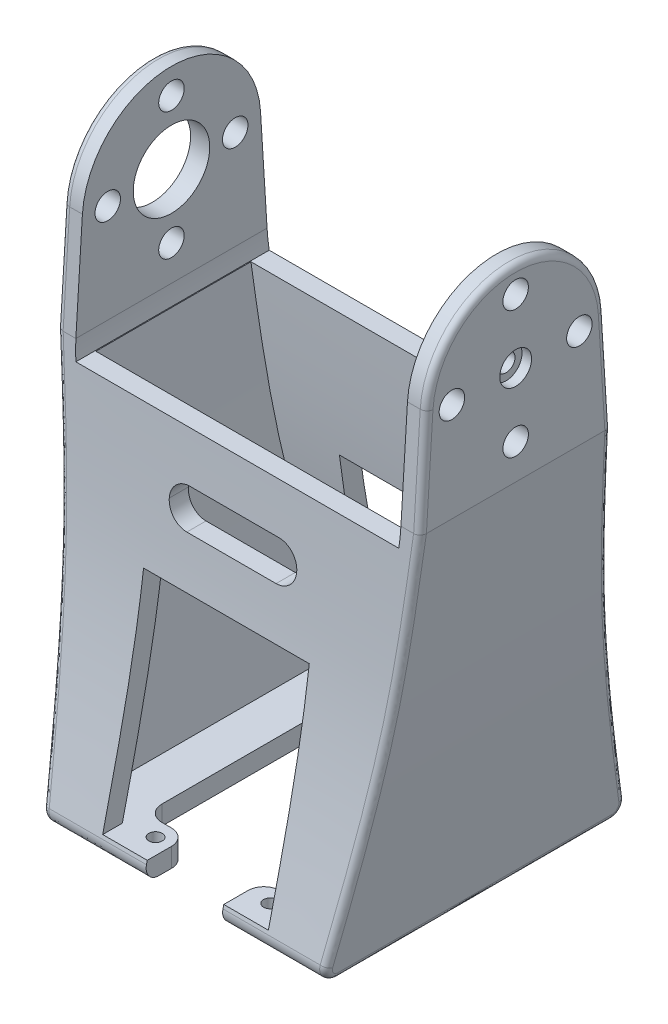
SolidWorks part; units mm, degrees
material "Esun Hard Tough Resin"
ref_plane "Front Plane" through (0, 0, 0) normal (0, 0, 1) x (1, 0, 0)
ref_plane "Top Plane" through (0, 0, 0) normal (0, 1, 0) x (1, 0, 0)
ref_plane "Right Plane" through (0, 0, 0) normal (1, 0, 0) x (0, 0, -1)
sketch "Sketch2" plane through (0, 0, 0) normal (0, 1, 0) x (1, 0, 0)
  line L1 (22, -24) -> (-22, -24)
  line L2 (22, -24) -> (22, 24)
  line L3 (22, 24) -> (-22, 24)
  line L4 (-22, -24) -> (-22, 24)
  line L5 (22, -24) -> (-22, 24) construction
  line L6 (22, 24) -> (-22, -24) construction
  point P0 (0, 0)
  dimension "D1" = 48
  dimension "D2" = 44
ref_plane "Plane1" through (0, 60, 0) normal (0, 1, 0) x (1, 0, 0)
ref_plane "Plane6" through (0, 35, 0) normal (0, 1, 0) x (1, 0, 0)
sketch "Sketch29" plane through (0, 35, 0) normal (0, 1, 0) x (1, 0, 0)
  line L1 (-26, -17) -> (26, -17)
  line L2 (-26, -17) -> (-26, 17)
  line L3 (-26, 17) -> (26, 17)
  line L4 (26, -17) -> (26, 17)
  line L5 (-26, -17) -> (26, 17) construction
  line L6 (-26, 17) -> (26, -17) construction
  point P0 (0, 0)
  dimension "D1" = 52
  dimension "D2" = 34
sketch "Sketch3" plane through (0, 60, 0) normal (0, 1, 0) x (1, 0, 0)
  line L1 (28.5, -15) -> (-28.5, -15)
  line L2 (28.5, -15) -> (28.5, 15)
  line L3 (28.5, 15) -> (-28.5, 15)
  line L4 (-28.5, -15) -> (-28.5, 15)
  line L5 (28.5, -15) -> (-28.5, 15) construction
  line L6 (28.5, 15) -> (-28.5, -15) construction
  point P0 (0, 0)
  dimension "D1" = 57
  dimension "D2" = 30
loft "Loft1" add profiles "Sketch2", "Sketch29", "Sketch3" connector at (-22, 0, 24) connector at (-26, 35, 17) connector at (-28.5, 60, 15)
shell "Shell1" thickness 3
ref_plane "Plane2" through (0, 0, 25.5) normal (0, 0, 1) x (1, 0, 0)
ref_plane "Plane3" through (0, 0, 24) normal (0, 0, 1) x (1, 0, 0)
sketch "Sketch19" plane through (0, 60, 0) normal (0, 1, 0) x (1, 0, 0)
  line L0 (28.5, -15) -> (-28.5, -15) construction
  line L1 (28.5, -15) -> (28.5, 15) construction
  line L2 (28.5, 15) -> (-28.5, 15) construction
  line L3 (-28.5, -15) -> (-28.5, 15) construction
  line L4 (28.5, -15) -> (-28.5, -15)
  line L5 (28.5, -15) -> (28.5, 15)
  line L6 (28.5, 15) -> (-28.5, 15)
  line L7 (-28.5, -15) -> (-28.5, 15)
extrude "Boss-Extrude4" add sketch "Sketch19" along normal blind 30 separate body
sketch "Sketch21" plane through (0, 90, 0) normal (0, 1, 0) x (1, 0, 0)
  line L0 (28.5, 15) -> (-28.5, 15) construction
  line L1 (25.5, -15) -> (-25.5, -15)
  line L2 (25.5, -15) -> (25.5, 15)
  line L3 (25.5, 15) -> (-25.5, 15)
  line L4 (-25.5, -15) -> (-25.5, 15)
  line L5 (25.5, -15) -> (-25.5, 15) construction
  line L6 (25.5, 15) -> (-25.5, -15) construction
  point P0 (0, 0)
  dimension "D1" = 51
extrude "Cut-Extrude15" cut sketch "Sketch21" against normal blind 30
sketch "Sketch22" plane through (0, 0, 0) normal (1, 0, 0) x (0, 0, -1)
  line L0 (15, 90) -> (-15, 90) construction
  line L1 (15, 90) -> (-15, 90)
  line L2 (13.9725, 76.3766) -> (15, 60)
  line L3 (15, 60) -> (15, 90)
  line L4 (-15, 90) -> (-15, 60)
  line L5 (-15, 60) -> (-13.9725, 76.3766)
  circle A0 centre (0, 75.5) radius 6
  circle A1 centre (0, 75.5) radius 10 construction
  circle A2 centre (0, 75.5) radius 14
  circle A3 centre (0, 85.5) radius 2
  circle A4 centre (-10, 75.5) radius 2
  circle A5 centre (0, 65.5) radius 2
  circle A6 centre (10, 75.5) radius 2
  point P6 (0, 90)
  dimension "D1" = 28
  dimension "D2" = 20
  dimension "D3" = 12
  dimension "D4" = 4
  dimension "D5" = 14.5
extrude "Cut-Extrude17" cut sketch "Sketch22" against normal through all contours A2 L2 L3 L1 L4 L5 | A6 | A5 | A4 | A0 | A3 region at (0, 75, -14.5757) region at (0, 75.5, 0) region at (0, 85.5, 0) region at (0, 75.5, 10) region at (0, 65.5, 0) region at (0, 75.5, -10)
sketch "Sketch23" plane through (0, 0, 24) normal (0, 0, 1) x (1, 0, 0)
  line L2 (25.3312, 57) -> (-25.3312, 57)
  line L12 (0, 0) -> (0, 60) construction
  line L17 (-25.5, 76.3766) -> (-25.5, 60) construction
  line L19 (-25.5, 60) -> (25.5, 60)
  line L22 (-25.5, 76.3766) -> (-25.5, 60) construction
  arc A0 (-25.5, 60) -> (-25.3312, 57) centre (1.2382, 60) ccw
  arc A1 (25.5, 60) -> (25.3312, 57) centre (-1.2382, 60) cw
  dimension "D1" = 3
extrude "Cut-Extrude26" cut sketch "Sketch23" against normal through all contours L2 L12 | L12 L2 | L2 A0 L19 A1 region at (0, 58.5017, 24)
sketch "Sketch24" plane through (-28.5, 0, 0) normal (-1, 0, 0) x (0, 0, 1)
  circle A0 centre (0, 85.5) radius 2
  circle A1 centre (10, 75.5) radius 2
  circle A2 centre (0, 65.5) radius 2
  circle A3 centre (-10, 75.5) radius 2
  dimension "D1" = 4
extrude "Cut-Extrude19" cut sketch "Sketch24" against normal through all
fillet "Fillet8" radius 2 2 edges
fillet "Fillet9" radius 1 10 edges at (22.1102, 0.9293, -23.1632) (-22.069, 0.5817, -22.884) (22.069, 0.5817, 22.884) (-22.1102, 0.9293, 23.1632)
sketch "Sketch25" plane through (28.5, 0, 0) normal (1, 0, 0) x (0, 0, -1)
  line L5 (-15, 90) -> (15, 90)
  line L7 (-13.9725, 76.3766) -> (-15, 60)
  line L8 (13.9725, 76.3766) -> (15, 60)
  line L9 (15, 60) -> (15, 90)
  line L10 (-15, 90) -> (-15, 60)
  arc A0 (13.9725, 76.3766) -> (-13.9725, 76.3766) centre (0, 75.5) ccw construction
  arc A1 (13.9725, 76.3766) -> (-13.9725, 76.3766) centre (0, 75.5) ccw
  circle A2 centre (0, 75.5) radius 6 construction
  circle A3 centre (0, 75.5) radius 6 construction
  circle A4 centre (0, 75.5) radius 1.4
  dimension "D1" = 2.8
extrude "Cut-Extrude20" cut sketch "Sketch25" against normal up to next (3 mm away)
sketch "Sketch26" plane through (28.5, 0, 0) normal (1, 0, 0) x (0, 0, -1)
  circle A0 centre (0, 75.5) radius 2.5
  dimension "D1" = 5
extrude "Cut-Extrude21" cut sketch "Sketch26" against normal blind 1.5
ref_plane "Plane4" through (0, 0, 23.4208) normal (0, 0, 1) x (1, 0, 0)
sketch "Sketch28" plane through (0, 0, 23.4208) normal (0, 0, 1) x (1, 0, 0)
  line L0 (0, 0) -> (0, 57) construction
  line L1 (-13, 3) -> (13, 3)
  line L2 (-13, 3) -> (-13, 36)
  line L3 (-13, 36) -> (13, 36)
  line L4 (13, 3) -> (13, 36)
  line L5 (-13, 3) -> (13, 36) construction
  line L6 (-13, 36) -> (13, 3) construction
  line L7 (-19.3346, 3) -> (19.3346, 3) construction
  line L8 (25.3312, 57) -> (-25.3312, 57) construction
  point P0 (0, 19.5)
  point P9 (0, 0)
  dimension "D1" = 33
  dimension "D2" = 26
extrude "Cut-Extrude23" cut sketch "Sketch28" against normal through all and the other way blind 10
sketch "Sketch30" plane through (0, 0, 24) normal (0, 0, 1) x (1, 0, 0)
  line L1 (-10, 43.5) -> (10, 43.5)
  line L2 (-10, 43.5) -> (-10, 49.5)
  line L3 (-10, 49.5) -> (10, 49.5)
  line L4 (10, 43.5) -> (10, 49.5)
  line L5 (-10, 43.5) -> (10, 49.5) construction
  line L6 (-10, 49.5) -> (10, 43.5) construction
  line L7 (0, 36) -> (0, 57) construction
  line L8 (-13, 36) -> (13, 36) construction
  line L9 (25.3312, 57) -> (-25.3312, 57) construction
  point P0 (0, 46.5)
  point P5 (0, 42.604)
  point P13 (0, 46.5)
  dimension "D1" = 6
  dimension "D2" = 20
extrude "Cut-Extrude27" cut sketch "Sketch30" against normal up to surface (10.9194 mm away) contours L3 L4 L1 L2 up to face at (-3.8528, 24.6718, 16.1355)
fillet "Fillet12" radius 3 4 edges at (10, 43.5, 14.5862) (10, 49.5, 14.1251) (-10, 49.5, 14.1251) (-10, 43.5, 14.5862)
sketch "Sketch13" plane through (0, 0, 0) normal (0, 1, 0) x (1, 0, 0)
  line L4 (-8.5007, 19.5) -> (-6.0007, 19.5) construction
  line L5 (-6.0007, 23.474) -> (-6.0007, 19.7118)
  line L32 (0, -23.4208) -> (0, 23.474) construction
  line L33 (-32.8899, -23.4208) -> (32.8899, -23.4208) construction
  line L36 (-6.0007, 23.474) -> (6.0007, 23.474)
  line L37 (-8.5007, 17.2118) -> (-10.0007, 17.2118)
  line L38 (-12.5007, 14.7118) -> (-12.5007, -14.5)
  line L41 (21.1115, 21.474) -> (21.1115, -21.474) construction
  line L45 (12.5007, 14.7118) -> (12.5007, -14.5)
  line L46 (8.5007, 17.2118) -> (10.0007, 17.2118)
  line L47 (6.0007, 23.474) -> (6.0007, 19.7118)
  line L48 (-6.0007, -23.474) -> (-6.0007, -19.5)
  line L49 (-8.5007, -17) -> (-10.0007, -17)
  line L50 (8.5007, -17) -> (10.0007, -17)
  line L51 (6.0007, -23.474) -> (6.0007, -19.5)
  line L52 (-6.0007, -23.474) -> (6.0007, -23.474)
  line L53 (21.2301, 23.474) -> (-21.2301, 23.474) construction
  line L60 (-21.2301, -23.474) -> (21.2301, -23.474) construction
  circle A0 centre (-8.5007, -8.8) radius 1.05
  circle A1 centre (-8.5007, -19.5) radius 1.05
  circle A2 centre (9.4993, -19.4996) radius 1.05
  circle A3 centre (9.4993, -8.8) radius 1.05
  circle A4 centre (-8.5007, 19.5) radius 1.05
  circle A5 centre (9.4993, 19.5) radius 1.05
  arc A6 (8.5007, 17.2118) -> (6.0007, 19.7118) centre (8.5007, 19.7118) cw
  arc A7 (-6.0007, 19.7118) -> (-8.5007, 17.2118) centre (-8.5007, 19.7118) cw
  arc A8 (-12.5007, -14.5) -> (-10.0007, -17) centre (-10.0007, -14.5) ccw
  arc A9 (8.5007, -17) -> (6.0007, -19.5) centre (8.5007, -19.5) ccw
  arc A10 (10.0007, -17) -> (12.5007, -14.5) centre (10.0007, -14.5) ccw
  arc A11 (12.5007, 14.7118) -> (10.0007, 17.2118) centre (10.0007, 14.7118) ccw
  arc A12 (-10.0007, 17.2118) -> (-12.5007, 14.7118) centre (-10.0007, 14.7118) ccw
  arc A13 (-6.0007, -19.5) -> (-8.5007, -17) centre (-8.5007, -19.5) ccw
  point P16 (6.0007, 17.2118)
  point P21 (0, -23.292)
  point P27 (-6.0007, 17.2118)
  point P30 (-12.5007, -17)
  point P45 (6.0007, -17)
  point P48 (12.5007, -17)
  point P51 (12.5007, 17.2118)
  point P54 (-12.5007, 17.2118)
  point P57 (-6.0007, -17)
  dimension "D2" = 2.1
  dimension "D6" = 2.5
  dimension "D11" = 2.5
  dimension "D12" = 2.5
  dimension "D13" = 2.5
  dimension "D14" = 8.6109
  dimension "D3" = 10.7
  dimension "D4" = 39
  dimension "D5" = 18
  dimension "D7" = 3.974
  dimension "D8" = 6.5
  dimension "D9" = 2.5
  dimension "D10" = 2.5
extrude "Cut-Extrude24" cut sketch "Sketch13" along normal up to next (3 mm away) contours A5 | A1 | A2 | L51 A9 L50 A10 L45 A11 L46 A6 L47 L36 L5 A7 L37 A12 L38 A8 L49 A13 L48 L52 | A4 region at (9.4993, 0, -19.5)
ref_plane "Plane5" through (0, 0, 16.8737) normal (0, 0, 1) x (1, 0, 0)
fillet "Fillet10" radius 1 3 edges at (-28.5, 68.1883, -14.4863) (-28.5, 89.5, 0) (-28.5, 68.1883, 14.4863)
fillet "Fillet11" radius 1 3 edges at (28.5, 68.1883, -14.4863) (28.5, 89.5, 0) (28.5, 68.1883, 14.4863)
ref_plane "Plane9" through (12.5007, 0, 0) normal (-1, 0, 0) x (0, 0, 1)
equation "\"D7@Sketch17\"=\"D2@Sketch17\""
equation "\"D7@Sketch18\"=\"D2@Sketch18\""
equation "\"D6@Sketch18\"=\"D2@Sketch18\""
equation "\"D6@Sketch17\"=\"D2@Sketch17\""
equation "\"D5@Sketch17\"=\"D2@Sketch17\""
equation "\"D4@Sketch17\"=\"D2@Sketch17\""
equation "\"D3@Sketch17\"=\"D2@Sketch17\""
